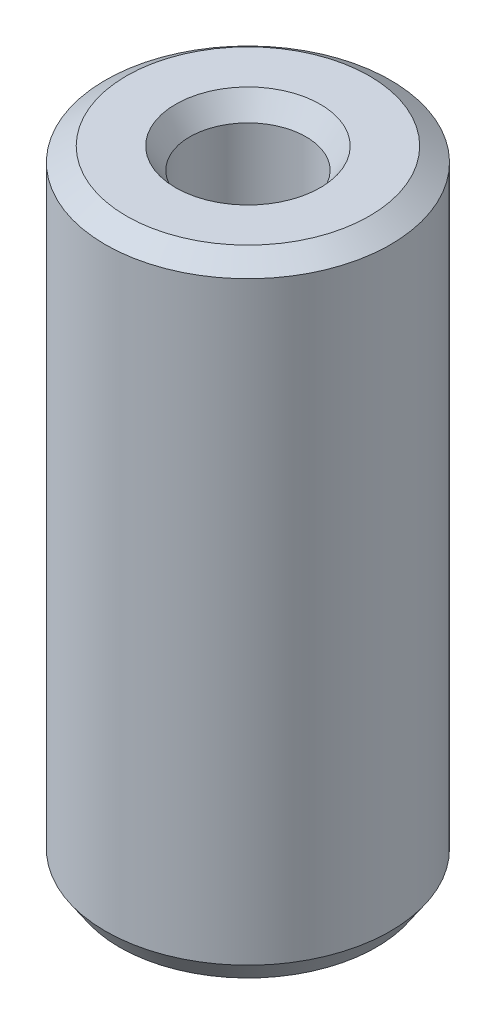
SolidWorks part; units mm, degrees
ref_plane "Front Plane" through (0, 0, 0) normal (0, 0, 1) x (1, 0, 0)
ref_plane "Top Plane" through (0, 0, 0) normal (0, 1, 0) x (1, 0, 0)
ref_plane "Right Plane" through (0, 0, 0) normal (1, 0, 0) x (0, 0, -1)
sketch "Sketch1" plane through (0, 0, 0) normal (0, 1, 0) x (1, 0, 0)
  circle A0 centre (0, 0) radius 40
  dimension "SLEEVE_OD" = 80
extrude "Boss-Extrude1" add sketch "Sketch1" along normal blind 176.7407
sketch "Sketch2" plane through (0, 0, 0) normal (0, 1, 0) x (1, 0, 0)
  circle A0 centre (0, 0) radius 16.3159
  dimension "BORE_D" = 32.6319
extrude "Cut-Extrude1" cut sketch "Sketch2" along normal through all
chamfer "Chamfer1" distance 3.9837 angle 56.05 4 edges at (0, 176.7407, 16.3159) (0, 0, 16.3159) (0, 0, 40) (0, 176.7407, 40) first distance on face at (0, 176.7407, 16.3159) first distance on face at (0, 0, 16.3159) first distance on face at (0, 176.7407, 40)
